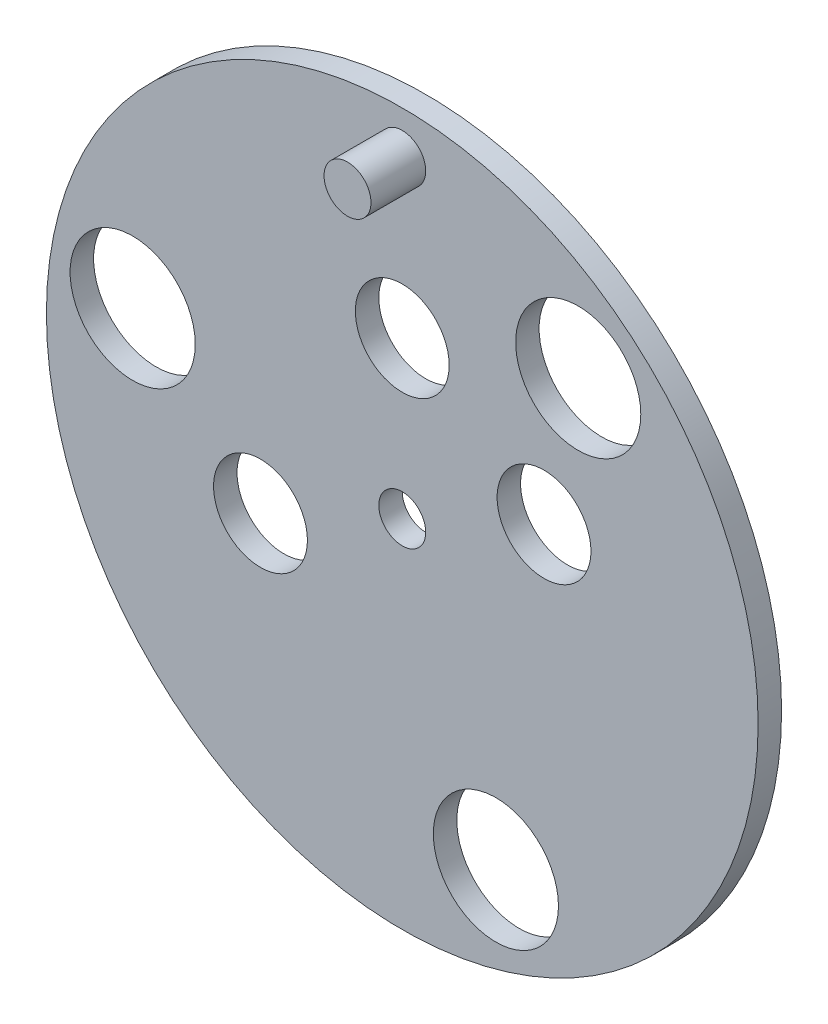
SolidWorks part; units mm, degrees
ref_plane "Front Plane" through (0, 0, 0) normal (0, 0, 1) x (1, 0, 0)
ref_plane "Top Plane" through (0, 0, 0) normal (0, 1, 0) x (1, 0, 0)
ref_plane "Right Plane" through (0, 0, 0) normal (1, 0, 0) x (0, 0, -1)
sketch "Sketch1" plane through (0, 0, 0) normal (0, 0, 1) x (1, 0, 0)
  circle A0 centre (0, 0) radius 227.5
  circle A1 centre (0, 200) radius 15
  dimension "D2" = 30
  dimension "D3" = 455
  dimension "D1" = 200
extrude "Boss-Extrude1" add sketch "Sketch1" along normal mid plane 15 contours A0
extrude "Boss-Extrude2" add sketch "Sketch1<3>" along normal up to surface (35 mm away) from surface contours A1 region at (0, 200, 0) starting at face at (227.5, 0, 7.5)
sketch "Sketch1<3>" plane through (0, 0, 0) normal (0, 0, 1) x (1, 0, 0) same geometry as "Sketch1"
sketch "Sketch2" plane through (0, 0, 7.5) normal (0, 0, 1) x (1, 0, 0)
  line L0 (90.6308, 42.2618) -> (-90.6308, -42.2618) construction
  line L1 (0, -100) -> (0, 100) construction
  line L2 (-172.3414, 30.3884) -> (0, 0) construction
  line L3 (59.8535, -164.4462) -> (0, 0) construction
  line L4 (0, 0) -> (112.4878, 134.0578) construction
  circle A0 centre (-172.3414, 30.3884) radius 40
  circle A2 centre (0, 100) radius 30
  circle A4 centre (90.6308, 42.2618) radius 30
  circle A9 centre (-90.6308, -42.2618) radius 30
  circle A10 centre (112.4878, 134.0578) radius 40
  circle A11 centre (59.8535, -164.4462) radius 40
  dimension "D1" = 60
  dimension "D4" = 100
  dimension "D8" = 60
  dimension "D11" = 3
  dimension "D12" = 120
  dimension "D7" = 80
  dimension "D2" = 100
  dimension "D6" = 175
  dimension "D3" = 100
  dimension "D9" = 115
  dimension "D10" = 80
  dimension "D13" = 120
extrude "Cut-Extrude1" cut sketch "Sketch2" against normal through all
sketch "Sketch3" plane through (0, 0, 0) normal (0, 0, 1) x (1, 0, 0)
  circle A0 centre (0, 0) radius 15
  dimension "D1" = 30
extrude "Cut-Extrude3" cut sketch "Sketch3" against normal up to surface (7.5 mm away) from surface contours A0 up to face at (-132.3414, 30.3884, -7.5) starting at face at (-132.3414, 30.3884, 7.5)
